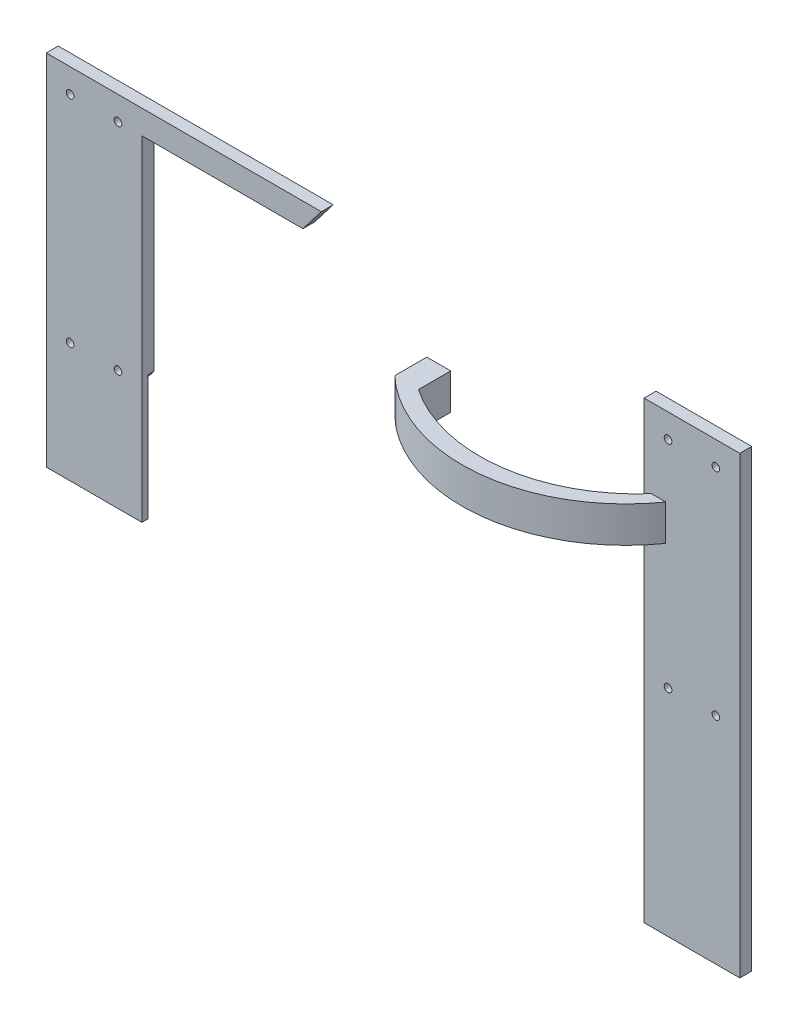
SolidWorks part; units mm, degrees
ref_plane "Front Plane" through (0, 0, 0) normal (0, 0, 1) x (1, 0, 0)
ref_plane "Top Plane" through (0, 0, 0) normal (0, 1, 0) x (1, 0, 0)
ref_plane "Right Plane" through (0, 0, 0) normal (1, 0, 0) x (0, 0, -1)
sketch "Sketch1" plane through (0, 0, 0) normal (0, 0, 1) x (1, 0, 0)
  line L0 (82.55, -20.32) -> (82.55, -6.35)
  line L2 (0, 0) -> (0, 157.48)
  line L4 (368.3, -20.32) -> (368.3, 106.68)
  line L5 (82.55, -6.35) -> (107.95, -6.35)
  line L6 (107.95, -6.35) -> (107.95, -20.32)
  line L7 (107.95, -20.32) -> (260.35, -20.32)
  line L8 (260.35, -20.32) -> (260.35, -6.35)
  line L9 (260.35, -6.35) -> (285.75, -6.35)
  line L10 (285.75, -6.35) -> (285.75, -20.32)
  line L11 (285.75, -20.32) -> (368.3, -20.32)
  line L12 (361.95, 12.7) -> (368.3, 12.7) construction
  line L13 (0, 0) -> (6.35, 0) construction
  line L14 (0.0315, -6.9818) -> (1.619, -22.8568)
  line L15 (8.6391, -28.5361) -> (82.55, -20.32)
  line L16 (0, 0) -> (0, -6.35)
  line L17 (85.725, 97.155) -> (82.9754, 95.5675) construction
  line L18 (97.0634, 115.6163) -> (58.5686, 93.3913) construction
  line L19 (97.0634, 115.6163) -> (107.3822, 97.7437) construction
  line L20 (58.5686, 93.3913) -> (68.8873, 75.5187) construction
  line L21 (107.3822, 97.7437) -> (68.8873, 75.5187) construction
  line L22 (97.0634, 115.6163) -> (68.8873, 75.5187) construction
  line L23 (58.5686, 93.3913) -> (107.3822, 97.7437) construction
  line L24 (7.9375, -22.225) -> (88.2169, 59.1366) construction
  line L25 (184.15, 62.98) -> (184.15, 197.98) construction
  line L26 (184.15, 197.98) -> (184.15, 332.98) construction
  line L27 (355.6, 335.28) -> (330.2, 335.28) construction
  line L28 (330.2, 335.28) -> (330.2, 220.98) construction
  line L29 (330.2, 220.98) -> (355.6, 220.98) construction
  line L30 (355.6, 220.98) -> (355.6, 335.28) construction
  line L31 (184.15, 347.98) -> (184.15, 269.4703) construction
  line L32 (12.7, 335.28) -> (38.1, 335.28) construction
  line L33 (38.1, 335.28) -> (38.1, 220.98) construction
  line L34 (12.7, 220.98) -> (12.7, 335.28) construction
  line L35 (38.1, 220.98) -> (12.7, 220.98) construction
  line L36 (194.15, 347.98) -> (211.6138, 341.63)
  line L37 (184.15, 347.98) -> (146.05, 347.98)
  line L38 (184.15, 347.98) -> (194.15, 347.98)
  line L39 (348.5362, 347.98) -> (413.4623, 347.98)
  line L40 (348.5362, 347.98) -> (211.6138, 347.98) construction
  line L42 (146.05, 347.98) -> (0, 157.48)
  line L44 (211.6138, 341.63) -> (211.6138, 205.74)
  line L45 (211.6138, 205.74) -> (368.3, 106.68)
  line L46 (194.15, 347.98) -> (-141.0713, 347.98) construction
  line L47 (136.3133, 335.28) -> (146.05, 347.98)
  line L48 (0, 157.48) -> (50.8, 157.48)
  line L49 (0, 157.48) -> (0, 347.98)
  line L50 (0, 347.98) -> (50.8, 347.98)
  line L51 (50.8, 157.48) -> (50.8, 347.98)
  line L52 (368.3, 106.68) -> (317.5011, 106.68)
  line L53 (368.3, 106.68) -> (368.3, 347.98)
  line L54 (368.3, 347.98) -> (317.5011, 347.98)
  line L55 (317.5011, 106.68) -> (317.5011, 347.98)
  line L60 (50.8, 347.98) -> (136.3133, 347.98)
  line L61 (50.8, 347.98) -> (50.8, 335.28)
  line L62 (50.8, 335.28) -> (136.3133, 335.28)
  line L63 (136.3133, 347.98) -> (136.3133, 335.28)
  line L64 (136.3133, 335.28) -> (126.5767, 335.28)
  line L65 (146.05, 347.98) -> (136.3133, 347.98)
  line L66 (126.5767, 335.28) -> (136.3133, 347.98)
  line L67 (211.6138, 341.63) -> (317.5011, 347.98)
  line L68 (0, 157.48) -> (50.8, 223.7409)
  line L73 (211.6138, 305.943) -> (198.9138, 305.943)
  line L74 (211.6138, 305.943) -> (211.6138, 286.893)
  line L75 (211.6138, 286.893) -> (198.9138, 286.893)
  line L76 (198.9138, 305.943) -> (198.9138, 286.893)
  line L77 (317.5011, 106.68) -> (368.3, 106.68)
  line L80 (368.3, 106.68) -> (368.3, 152.4)
  line L81 (0, 157.48) -> (50.8, 157.48)
  line L82 (0, 157.48) -> (0, 216.0864)
  line L84 (50.8, 157.48) -> (50.8, 216.0864)
  line L86 (317.5011, 106.68) -> (368.3, 106.68)
  line L87 (317.5011, 106.68) -> (317.5011, 81.28)
  line L88 (317.5011, 81.28) -> (368.3, 81.28)
  line L89 (368.3, 106.68) -> (368.3, 81.28)
  line L90 (0, 157.48) -> (50.8, 157.48)
  line L91 (0, 157.48) -> (0, 132.08)
  line L92 (0, 132.08) -> (50.8, 132.08)
  line L93 (50.8, 157.48) -> (50.8, 132.08)
  circle A0 centre (6.35, 0) radius 2.032
  circle A1 centre (6.35, 12.7) radius 2.032
  circle A2 centre (361.95, 0) radius 2.032
  circle A3 centre (361.95, 12.7) radius 2.032
  arc A5 (1.619, -22.8568) -> (8.6391, -28.5361) centre (7.9375, -22.225) ccw
  circle A6 centre (7.9375, -22.225) radius 2.032
  arc A7 (0, -6.35) -> (0.0315, -6.9818) centre (6.35, -6.35) ccw
  circle A8 centre (38.1, 78.105) radius 2.032
  circle A9 centre (85.725, 97.155) radius 2.032
  circle A10 centre (58.5686, 93.3913) radius 2.032
  circle A11 centre (68.8873, 75.5187) radius 2.032
  circle A12 centre (107.3822, 97.7437) radius 2.032
  circle A13 centre (97.0634, 115.6163) radius 2.032
  circle A14 centre (88.2169, 59.1366) radius 2.032
  circle A15 centre (184.15, 62.98) radius 2
  circle A16 centre (184.15, 197.98) radius 2
  circle A17 centre (184.15, 332.98) radius 2
  circle A18 centre (63.5, 316.23) radius 2.032
  circle A19 centre (101.6, 157.48) radius 2.032
  circle A20 centre (355.6, 335.28) radius 2.032
  circle A21 centre (330.2, 335.28) radius 2.032
  circle A22 centre (355.6, 220.98) radius 2.032
  circle A23 centre (330.2, 220.98) radius 2.032
  circle A24 centre (12.7, 335.28) radius 2.032
  circle A25 centre (38.1, 335.28) radius 2.032
  circle A26 centre (12.7, 220.98) radius 2.032
  circle A27 centre (38.1, 220.98) radius 2.032
  circle A28 centre (202.8819, 335.28) radius 2
  point P82 (184.15, 347.98)
  point P83 (202.8819, 344.805)
  point P102 (198.9138, 296.418)
  dimension "D6" = 4.064
  dimension "D10" = 6.35
  dimension "D11" = 4.064
  dimension "D17" = 38.1
  dimension "D27" = 4
  dimension "D31" = 4.064
  dimension "D32" = 38.1
  dimension "D36" = 4.064
  dimension "D47" = 50.8
  dimension "D2" = 127
  dimension "D3" = 13.97
  dimension "D4" = 25.4
  dimension "D5" = 152.4
  dimension "D7" = 12.7
  dimension "D8" = 6.35
  dimension "D9" = 20.32
  dimension "D12" = 22.225
  dimension "D13" = 1.5875
  dimension "D14" = 82.55
  dimension "D15" = 368.3
  dimension "D16" = 6.35
  dimension "D18" = 98.425
  dimension "D19" = 47.625
  dimension "D20" = 19.05
  dimension "D21" = 3.175
  dimension "D22" = 60
  dimension "D23" = 20.6375
  dimension "D24" = 44.45
  dimension "D25" = 38.1
  dimension "D26" = 114.3
  dimension "D28" = 135
  dimension "D29" = 12.7
  dimension "D30" = 15
  dimension "D33" = 63.5
  dimension "D34" = 27.4638
  dimension "D35" = 101.6
  dimension "D37" = 114.3
  dimension "D38" = 25.4
  dimension "D39" = 12.7
  dimension "D40" = 157.48
  dimension "D41" = 142.24
  dimension "D42" = 368.3
  dimension "D43" = 10
  dimension "D44" = 6.35
  dimension "D45" = 31.75
  dimension "D46" = 6.35
  dimension "D48" = 50.7989
  dimension "D49" = 19.05
  dimension "D50" = 12.7
  dimension "D51" = 45.212
  dimension "D52" = 12.7
  dimension "D53" = 25.4
  dimension "D54" = 25.4
extrude "Boss-Extrude1" add sketch "Sketch1" along normal blind 6.35 contours L48 L51 L42 | L42 L51 L50 L49 A26 A24 A25 A27 | L62 L66 L60 L51 | L66 L62 L63 | L42 L65 L63 | L73 L76 L75 L44 | L55 L45 L53 L39 L54 A23 A22 A21 A20 | L55 L52 L45
sketch "Sketch5" plane through (0, 0, 6.35) normal (0, 0, 1) x (1, 0, 0)
  line L0 (211.6138, 305.943) -> (198.9138, 305.943) construction
  line L1 (198.9138, 305.943) -> (211.6138, 305.943)
  line L2 (198.9138, 305.943) -> (198.9138, 286.893)
  line L3 (198.9138, 286.893) -> (211.6138, 286.893)
  line L4 (211.6138, 305.943) -> (211.6138, 286.893)
  line L5 (198.9138, 305.943) -> (198.9138, 286.893) construction
  line L6 (211.6138, 305.943) -> (211.6138, 286.893) construction
  point P4 (198.9138, 286.9002)
  point P5 (211.6138, 286.893)
  point P6 (198.9138, 286.893)
extrude "Boss-Extrude4" add sketch "Sketch5" along normal blind 18.415
sketch "Sketch4" plane through (0, 305.943, 0) normal (0, 1, 0) x (1, 0, 0)
  line L2 (321.3418, -6.35) -> (328.9618, -6.35)
  line L3 (198.9138, -20.32) -> (211.6138, -20.32)
  line L4 (211.6138, -24.765) -> (211.6138, 0) construction
  line L5 (198.9138, -24.765) -> (198.9138, 0) construction
  line L6 (317.5011, -6.35) -> (368.3, -6.35) construction
  line L7 (211.6138, 0) -> (198.9138, 0) construction
  arc A0 (211.6138, -20.32) -> (321.3418, -6.35) centre (258.5435, 48.9847) ccw
  arc A1 (198.9138, -20.32) -> (328.9618, -6.35) centre (257.8345, 43.4808) ccw
  dimension "D1" = 130.048
  dimension "D2" = 20.32
  dimension "D3" = 7.62
extrude "Boss-Extrude5" add sketch "Sketch4" against normal up to surface (19.05 mm away) up to face at (205.2638, 286.893, 12.3825)
sketch "Sketch6" plane through (0, 305.943, 0) normal (0, 1, 0) x (1, 0, 0)
  line L0 (204.125, -24.765) -> (198.9138, -20.1235)
  line L1 (198.9138, -24.765) -> (198.9138, 0) construction
  line L2 (198.9138, -20.1235) -> (198.9138, -24.765)
  line L3 (198.9138, -24.765) -> (204.125, -24.765)
extrude "Cut-Extrude1" cut sketch "Sketch6" against normal blind 20.955
sketch "Sketch7" plane through (0, 0, 0) normal (0, 0, -1) x (-1, 0, 0)
  line L2 (-211.6138, 305.943) -> (-211.6138, 286.893) construction
  line L3 (-211.6138, 305.943) -> (-198.9138, 305.943) construction
  circle A0 centre (-205.2638, 296.418) radius 2.032
  point P5 (-211.6138, 296.418)
  point P8 (-205.2638, 305.943)
  dimension "D1" = 4.064
sketch "Sketch9" plane through (0, 0, 0) normal (0, 0, 1) x (1, 0, 0)
  line L0 (82.55, -20.32) -> (82.55, -6.35)
  line L2 (0, 0) -> (0, 157.48)
  line L4 (368.3, -20.32) -> (368.3, 106.68)
  line L5 (82.55, -6.35) -> (107.95, -6.35)
  line L6 (107.95, -6.35) -> (107.95, -20.32)
  line L7 (107.95, -20.32) -> (260.35, -20.32)
  line L8 (260.35, -20.32) -> (260.35, -6.35)
  line L9 (260.35, -6.35) -> (285.75, -6.35)
  line L10 (285.75, -6.35) -> (285.75, -20.32)
  line L11 (285.75, -20.32) -> (368.3, -20.32)
  line L12 (361.95, 12.7) -> (368.3, 12.7) construction
  line L13 (0, 0) -> (6.35, 0) construction
  line L14 (0.0315, -6.9818) -> (1.619, -22.8568)
  line L15 (8.6391, -28.5361) -> (82.55, -20.32)
  line L16 (0, 0) -> (0, -6.35)
  line L17 (85.725, 97.155) -> (82.9754, 95.5675) construction
  line L18 (97.0634, 115.6163) -> (58.5686, 93.3913) construction
  line L19 (97.0634, 115.6163) -> (107.3822, 97.7437) construction
  line L20 (58.5686, 93.3913) -> (68.8873, 75.5187) construction
  line L21 (107.3822, 97.7437) -> (68.8873, 75.5187) construction
  line L22 (97.0634, 115.6163) -> (68.8873, 75.5187) construction
  line L23 (58.5686, 93.3913) -> (107.3822, 97.7437) construction
  line L24 (7.9375, -22.225) -> (88.2169, 59.1366) construction
  line L25 (184.15, 62.98) -> (184.15, 197.98) construction
  line L26 (184.15, 197.98) -> (184.15, 332.98) construction
  line L27 (355.6, 335.28) -> (330.2, 335.28) construction
  line L28 (330.2, 335.28) -> (330.2, 220.98) construction
  line L29 (330.2, 220.98) -> (355.6, 220.98) construction
  line L30 (355.6, 220.98) -> (355.6, 335.28) construction
  line L31 (184.15, 347.98) -> (184.15, 269.4703) construction
  line L32 (12.7, 335.28) -> (38.1, 335.28) construction
  line L33 (38.1, 335.28) -> (38.1, 220.98) construction
  line L34 (12.7, 220.98) -> (12.7, 335.28) construction
  line L35 (38.1, 220.98) -> (12.7, 220.98) construction
  line L36 (194.15, 347.98) -> (211.6138, 341.63)
  line L37 (184.15, 347.98) -> (146.05, 347.98)
  line L38 (184.15, 347.98) -> (194.15, 347.98)
  line L39 (348.5362, 347.98) -> (413.4623, 347.98)
  line L40 (348.5362, 347.98) -> (211.6138, 347.98) construction
  line L42 (146.05, 347.98) -> (0, 157.48)
  line L44 (211.6138, 341.63) -> (211.6138, 205.74)
  line L45 (211.6138, 205.74) -> (368.3, 106.68)
  line L46 (194.15, 347.98) -> (-141.0713, 347.98) construction
  line L47 (136.3133, 335.28) -> (146.05, 347.98)
  line L48 (0, 157.48) -> (50.8, 157.48)
  line L49 (0, 157.48) -> (0, 347.98)
  line L50 (0, 347.98) -> (50.8, 347.98)
  line L51 (50.8, 157.48) -> (50.8, 347.98)
  line L52 (368.3, 106.68) -> (317.5011, 106.68)
  line L53 (368.3, 106.68) -> (368.3, 347.98)
  line L54 (368.3, 347.98) -> (317.5011, 347.98)
  line L55 (317.5011, 106.68) -> (317.5011, 347.98)
  line L60 (50.8, 347.98) -> (136.3133, 347.98)
  line L61 (50.8, 347.98) -> (50.8, 335.28)
  line L62 (50.8, 335.28) -> (136.3133, 335.28)
  line L63 (136.3133, 347.98) -> (136.3133, 335.28)
  line L64 (136.3133, 335.28) -> (126.5767, 335.28)
  line L65 (146.05, 347.98) -> (136.3133, 347.98)
  line L66 (126.5767, 335.28) -> (136.3133, 347.98)
  line L67 (211.6138, 341.63) -> (317.5011, 347.98)
  line L68 (0, 157.48) -> (50.8, 223.7409)
  line L73 (211.6138, 310.515) -> (198.9138, 310.515)
  line L74 (211.6138, 310.515) -> (211.6138, 271.145)
  line L75 (211.6138, 271.145) -> (198.9138, 271.145)
  line L76 (198.9138, 310.515) -> (198.9138, 271.145)
  line L77 (317.5011, 106.68) -> (368.3, 106.68)
  line L78 (317.5011, 106.68) -> (317.5011, 152.4)
  line L79 (317.5011, 152.4) -> (368.3, 152.4)
  line L80 (368.3, 106.68) -> (368.3, 152.4)
  line L81 (0, 157.48) -> (50.8, 157.48)
  line L82 (0, 157.48) -> (0, 216.0864)
  line L83 (0, 216.0864) -> (50.8, 216.0864)
  line L84 (50.8, 157.48) -> (50.8, 216.0864)
  line L85 (50.8, 223.7409) -> (50.8, 157.48)
  line L86 (368.3, 106.68) -> (317.5011, 138.796)
  line L87 (317.5011, 138.796) -> (368.3, 106.68)
  line L88 (317.5011, 138.796) -> (266.7022, 138.796)
  line L89 (368.3, 106.68) -> (317.5011, 106.68)
  line L90 (266.7022, 138.796) -> (317.5011, 106.68)
  line L91 (0, 157.48) -> (50.8, 223.7409)
  line L92 (0, 157.48) -> (0, 91.2191)
  line L93 (50.8, 223.7409) -> (50.8, 157.48)
  line L94 (0, 91.2191) -> (50.8, 157.48)
  circle A0 centre (6.35, 0) radius 2.032
  circle A1 centre (6.35, 12.7) radius 2.032
  circle A2 centre (361.95, 0) radius 2.032
  circle A3 centre (361.95, 12.7) radius 2.032
  arc A5 (1.619, -22.8568) -> (8.6391, -28.5361) centre (7.9375, -22.225) ccw
  circle A6 centre (7.9375, -22.225) radius 2.032
  arc A7 (0, -6.35) -> (0.0315, -6.9818) centre (6.35, -6.35) ccw
  circle A8 centre (38.1, 78.105) radius 2.032
  circle A9 centre (85.725, 97.155) radius 2.032
  circle A10 centre (58.5686, 93.3913) radius 2.032
  circle A11 centre (68.8873, 75.5187) radius 2.032
  circle A12 centre (107.3822, 97.7437) radius 2.032
  circle A13 centre (97.0634, 115.6163) radius 2.032
  circle A14 centre (88.2169, 59.1366) radius 2.032
  circle A15 centre (184.15, 62.98) radius 2
  circle A16 centre (184.15, 197.98) radius 2
  circle A17 centre (184.15, 332.98) radius 2
  circle A18 centre (63.5, 316.23) radius 2.032
  circle A19 centre (101.6, 157.48) radius 2.032
  circle A20 centre (355.6, 335.28) radius 2.032
  circle A21 centre (330.2, 335.28) radius 2.032
  circle A22 centre (355.6, 220.98) radius 2.032
  circle A23 centre (330.2, 220.98) radius 2.032
  circle A24 centre (12.7, 335.28) radius 2.032
  circle A25 centre (38.1, 335.28) radius 2.032
  circle A26 centre (12.7, 220.98) radius 2.032
  circle A27 centre (38.1, 220.98) radius 2.032
  circle A28 centre (202.8819, 335.28) radius 2
  circle A29 centre (205.2638, 296.418) radius 2.032
  point P82 (184.15, 347.98)
  point P83 (202.8819, 344.805)
  point P105 (0, 0)
  point P109 (198.9138, 290.83)
  dimension "D6" = 4.064
  dimension "D10" = 6.35
  dimension "D11" = 4.064
  dimension "D17" = 38.1
  dimension "D27" = 4
  dimension "D31" = 4.064
  dimension "D32" = 38.1
  dimension "D36" = 4.064
  dimension "D47" = 50.8
  dimension "D54" = 4.064
  dimension "D2" = 127
  dimension "D3" = 13.97
  dimension "D4" = 25.4
  dimension "D5" = 152.4
  dimension "D7" = 12.7
  dimension "D8" = 6.35
  dimension "D9" = 20.32
  dimension "D12" = 22.225
  dimension "D13" = 1.5875
  dimension "D14" = 82.55
  dimension "D15" = 368.3
  dimension "D16" = 6.35
  dimension "D18" = 98.425
  dimension "D19" = 47.625
  dimension "D20" = 19.05
  dimension "D21" = 3.175
  dimension "D22" = 60
  dimension "D23" = 20.6375
  dimension "D24" = 44.45
  dimension "D25" = 38.1
  dimension "D26" = 114.3
  dimension "D28" = 135
  dimension "D29" = 12.7
  dimension "D30" = 15
  dimension "D33" = 63.5
  dimension "D34" = 27.4638
  dimension "D35" = 101.6
  dimension "D37" = 114.3
  dimension "D38" = 25.4
  dimension "D39" = 12.7
  dimension "D40" = 157.48
  dimension "D41" = 142.24
  dimension "D42" = 368.3
  dimension "D43" = 10
  dimension "D44" = 6.35
  dimension "D45" = 31.75
  dimension "D46" = 6.35
  dimension "D48" = 50.7989
  dimension "D49" = 39.37
  dimension "D50" = 12.7
  dimension "D51" = 50.8
  dimension "D52" = 12.7
  dimension "D53" = 45.72
extrude "Cut-Extrude2" cut sketch "Sketch9" along normal blind 3.175 contours L91 L92 L94 L93 | L87 L88 L90 L89 | L74 L73 L76 L75
sketch "Sketch10" plane through (0, 0, 3.175) normal (0, 0, -1) x (-1, 0, 0)
  circle A0 centre (-205.2638, 296.418) radius 2.032
  dimension "D1" = 4.064
extrude "Cut-Extrude3" cut sketch "Sketch10" against normal blind 19.05
mirror "Mirror1" [suppressed] of bodies 125 129 126
delete or keep bodies "Body-Delete/Keep 1" [suppressed] type delete bodies bodies 125 129
